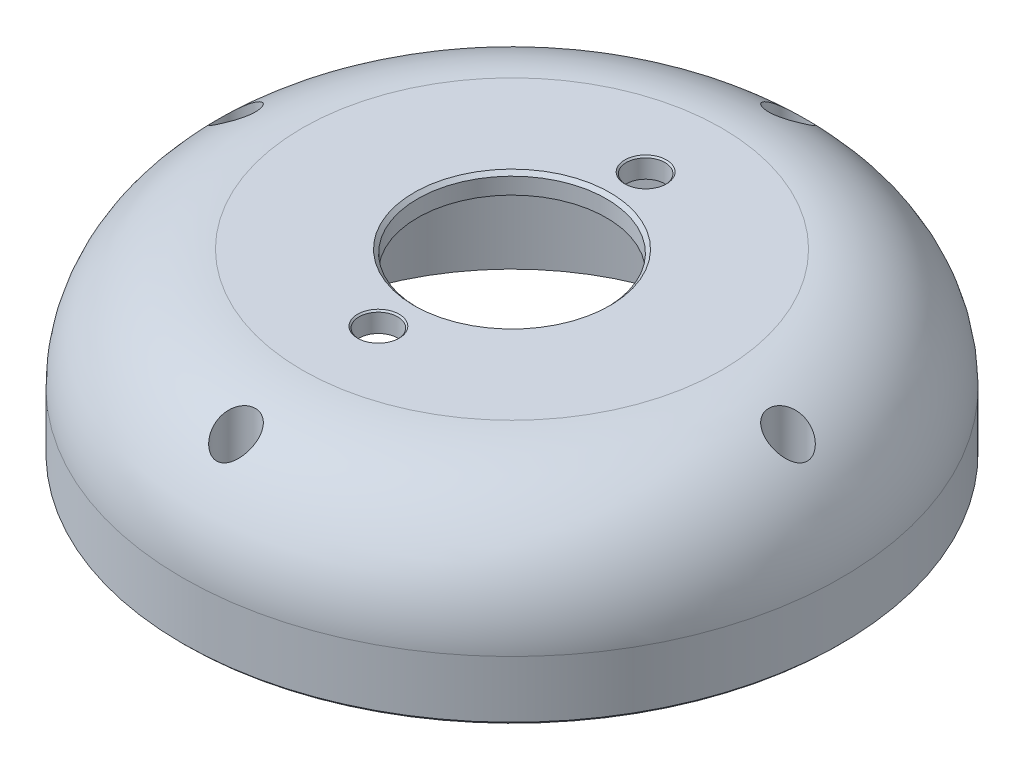
SolidWorks part; units mm, degrees
ref_plane "Front Plane" through (0, 0, 0) normal (0, 0, 1) x (1, 0, 0)
ref_plane "Top Plane" through (0, 0, 0) normal (0, 1, 0) x (1, 0, 0)
ref_plane "Right Plane" through (0, 0, 0) normal (1, 0, 0) x (0, 0, -1)
sketch "Sketch1" plane through (0, 0, 0) normal (0, 1, 0) x (1, 0, 0)
  circle A0 centre (0, 0) radius 11.5
  circle A1 centre (0, 0) radius 16.5
  dimension "D1" = 5
  dimension "D2" = 33
extrude "Boss-Extrude1" add sketch "Sketch1" along normal blind 8
sketch "Sketch2" plane through (0, 8, 0) normal (0, 1, 0) x (1, 0, 0)
  circle A0 centre (0, 0) radius 16.5
extrude "Boss-Extrude2" add sketch "Sketch2" along normal blind 1
scale "Scale1" scale about centroid uniform scaling yes scale factor 1.666667
sketch "Sketch3" plane through (0, 11.7467, 0) normal (0, 1, 0) x (1, 0, 0)
  line L0 (0, 13) -> (0, 11.15)
  line L1 (0, -12.95) -> (0, -11.15)
  line L10 (0, 11.15) -> (0, 0)
  line L11 (0, 0) -> (0, -11.15)
  circle A0 centre (0, 0) radius 7.875
  circle A4 centre (0, 11.15) radius 1.6125
  circle A5 centre (0, -11.15) radius 1.6125
  dimension "D1" = 15.75
  dimension "D8" = 3.225
  dimension "D9" = 1.8
  dimension "D10" = 3.225
  dimension "D2" = 11.15
  dimension "D3" = 11.15
extrude "Cut-Extrude1" cut sketch "Sketch3" against normal blind 9.65 contours A0 | A4 | A5 | A0 | A4 | A5 region at (0.6844, 11.7467, -11.15) region at (0.6844, 11.7467, 11.15) region at (-3.3423, 11.7467, 0)
chamfer "Chamfer2" distance 0.125 angle 45 2 edges at (0, 11.7467, -9.5375) (0, 11.7467, 12.7625)
chamfer "Chamfer4" distance 0.25 angle 45 1 edges at (0, -3.2533, 27.5)
sketch "Sketch4" plane through (0, 11.7467, 0) normal (0, 1, 0) x (1, 0, 0)
  circle A0 centre (23.03, 0) radius 1.6125
  circle A1 centre (0, 23.03) radius 1.6125
  circle A2 centre (0, -23.03) radius 1.6125
  circle A3 centre (-23.03, 0) radius 1.6125
  point P11 (0, 0)
  dimension "D2" = 3.225
  dimension "D1" = 4
extrude "Cut-Extrude2" cut sketch "Sketch4" against normal through all
chamfer "Chamfer6" distance 0.3 angle 45 1 edges at (0, 11.7467, 7.875)
chamfer "Chamfer7" distance 0.125 angle 45 4 edges at (-23.03, 11.7467, 1.6125) (0, 11.7467, 24.6425) (23.03, 11.7467, 1.6125) (0, 11.7467, -21.4175)
fillet "Fillet1" radius 10 1 edges at (0, 11.7467, 27.5)
